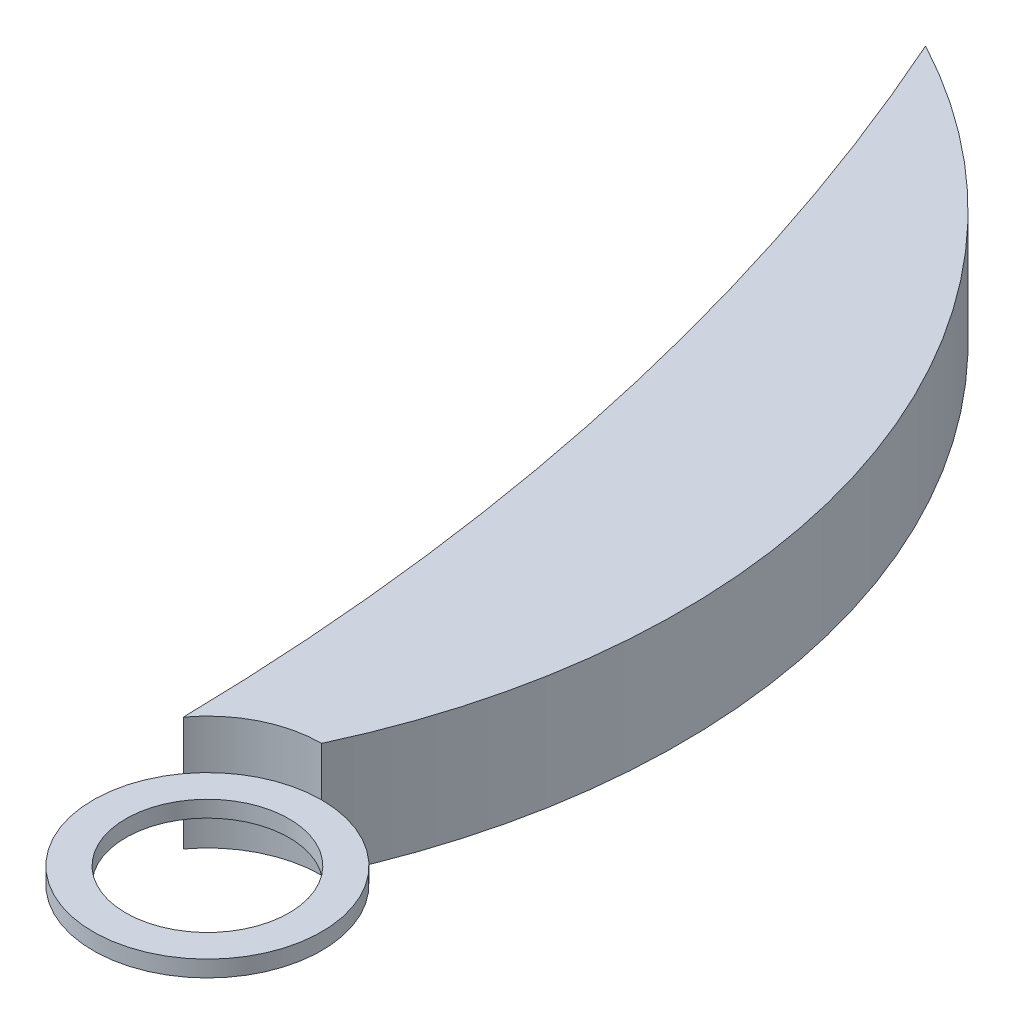
SolidWorks part; units mm, degrees
material "Galvanized Steel"
ref_plane "Front Plane" through (0, 0, 0) normal (0, 0, 1) x (1, 0, 0)
ref_plane "Top Plane" through (0, 0, 0) normal (0, 1, 0) x (1, 0, 0)
ref_plane "Right Plane" through (0, 0, 0) normal (1, 0, 0) x (0, 0, -1)
sketch "Sketch2" plane through (0, 0, 0) normal (0, 1, 0) x (1, 0, 0)
  line L0 (0, 0) -> (0, 355.6)
  arc A0 (-285.9696, 211.3593) -> (0, 355.6) centre (0, 0) ccw
  arc A1 (0, 355.6) -> (-939.8, 3175) centre (-1955.8, 1270) ccw
  arc A2 (-939.8, 3175) -> (-285.9696, 211.3593) centre (1219.2, 2097.3693) ccw
  dimension "D1" = 711.2
  dimension "D2" = 4318
  dimension "D7" = 4826
  dimension "D3" = 1955.8
  dimension "D4" = 285.9696
  dimension "D8" = 1219.2
extrude "Boss-Extrude1" add sketch "Sketch2" along normal blind 355.6 contours A1 A2 A0 region at (-440.4199, 0, -1459.5462)
sketch "Sketch5" plane through (0, 355.6, 0) normal (0, 1, 0) x (1, 0, 0)
  circle A0 centre (0, 0) radius 355.6
  dimension "D1" = 711.2
extrude "Cut-Extrude2" cut sketch "Sketch5" against normal blind 152.4
sketch "Sketch6" plane through (0, 0, 0) normal (0, -1, 0) x (1, 0, 0)
  circle A0 centre (0, 0) radius 355.6
  dimension "D1" = 711.2
extrude "Cut-Extrude3" cut sketch "Sketch6" against normal blind 152.4
sketch "Sketch7" plane through (0, 203.2, 0) normal (0, 1, 0) x (1, 0, 0)
  circle A0 centre (0, 0) radius 254
  dimension "D1" = 508
extrude "Cut-Extrude4" cut sketch "Sketch7" against normal blind 152.4
sketch "Sketch8" plane through (0, 0, 0) normal (0, -1, 0) x (1, 0, 0)
  arc A0 (-939.8, -3175) -> (-285.9696, -211.3593) centre (-7904.9124, -84.4322) ccw
  arc A3 (-939.8, -3175) -> (0, -355.6) centre (-1955.8, -1270) ccw
  arc A4 (-285.9696, -211.3593) -> (0, -355.6) centre (0, 0) ccw
  arc A5 (-285.9696, -211.3593) -> (-939.8, -3175) centre (1219.2, -2097.3693) ccw
  arc A6 (-939.8, -3175) -> (0, -355.6) centre (-1955.8, -1270) ccw
  arc A7 (-285.9696, -211.3593) -> (0, -355.6) centre (0, 0) ccw
  arc A8 (-285.9696, -211.3593) -> (-939.8, -3175) centre (1219.2, -2097.3693) ccw
  arc M6 (-285.9696, -211.3593) -> (-939.8, -3175) centre (1219.2, -2097.3693) ccw
  dimension "D2" = 7620
  dimension "D1" = 0
extrude "Cut-Extrude5" cut sketch "Sketch8" against normal blind 635 contours A0 M6 region at (-765.6602, 0, -1659.4748)
ref_plane "Plane1" through (0, 177.8, 0) normal (0, 1, 0) x (1, 0, 0)
ref_axis "Axis2" through (0, 177.8, -3351.53) along (0, 0, 1)
scale "Scale1" scale about centroid uniform scaling yes scale factor 0.214286
